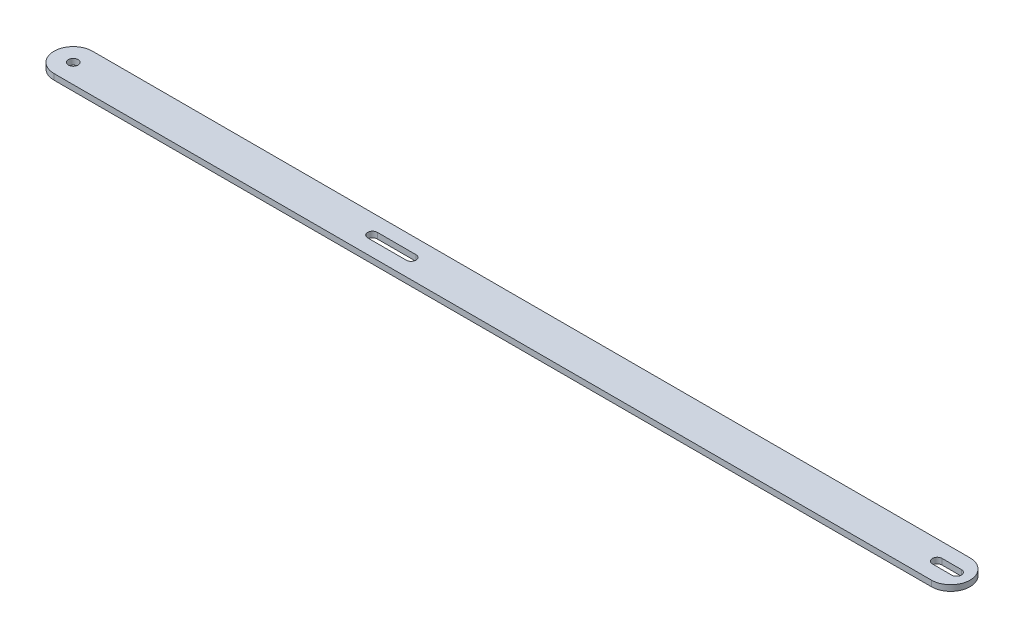
SolidWorks part; units mm, degrees
ref_plane "Front Plane" through (0, 0, 0) normal (0, 0, 1) x (1, 0, 0)
ref_plane "Top Plane" through (0, 0, 0) normal (0, 1, 0) x (1, 0, 0)
ref_plane "Right Plane" through (0, 0, 0) normal (1, 0, 0) x (0, 0, -1)
sketch "Sketch1" plane through (0, 0, 0) normal (0, 1, 0) x (1, 0, 0)
  line L0 (-227.25, 0) -> (227.25, 0) construction
  line L1 (-227.25, 10) -> (227.25, 10)
  line L2 (-227.25, -10) -> (227.25, -10)
  line L3 (230.25, 0) -> (220.25, 0) construction
  line L4 (230.25, -2.5) -> (220.25, -2.5)
  line L5 (230.25, 2.5) -> (220.25, 2.5)
  arc A0 (-227.25, 10) -> (-227.25, -10) centre (-227.25, 0) ccw
  arc A1 (227.25, -10) -> (227.25, 10) centre (227.25, 0) ccw
  circle A3 centre (-227.25, 0) radius 2.5
  arc A4 (230.25, -2.5) -> (230.25, 2.5) centre (230.25, 0) ccw
  arc A5 (220.25, 2.5) -> (220.25, -2.5) centre (220.25, 0) ccw
  point P2 (0, 0)
  point P12 (225.25, 0)
  dimension "D1" = 10
  dimension "D2" = 5
  dimension "D4" = 2.5
  dimension "D3" = 454.5
  dimension "D5" = 10
  dimension "D6" = 2
extrude "Boss-Extrude1" add sketch "Sketch1" along normal blind 3
sketch "Sketch2" plane through (0, 3, 0) normal (0, 1, 0) x (1, 0, 0)
  line L0 (-72.25, 0) -> (-52.25, 0) construction
  line L1 (-72.25, 2.5) -> (-52.25, 2.5)
  line L2 (-72.25, -2.5) -> (-52.25, -2.5)
  arc A0 (-72.25, 2.5) -> (-72.25, -2.5) centre (-72.25, 0) ccw
  arc A1 (-52.25, -2.5) -> (-52.25, 2.5) centre (-52.25, 0) ccw
  arc A3 (-227.25, 10) -> (-227.25, -10) centre (-227.25, 0) ccw construction
  point P2 (-62.25, 0)
  dimension "D1" = 165
  dimension "D3" = 2.5
  dimension "D2" = 20
extrude "Cut-Extrude1" cut sketch "Sketch2" against normal through all
